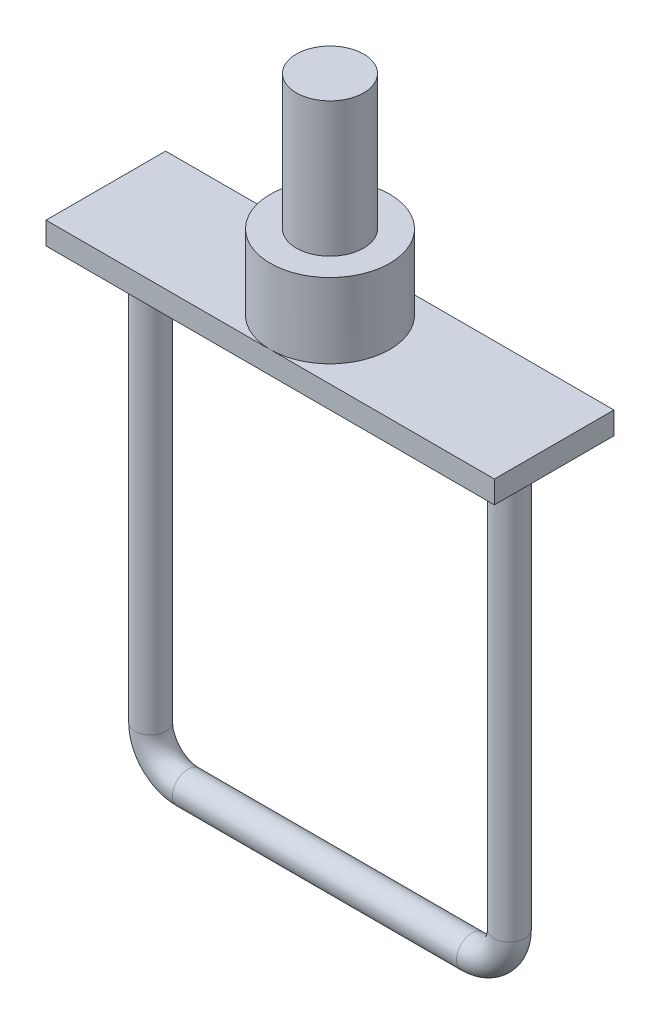
SolidWorks part; units mm, degrees
ref_plane "Front Plane" through (0, 0, 0) normal (0, 0, 1) x (1, 0, 0)
ref_plane "Top Plane" through (0, 0, 0) normal (0, 1, 0) x (1, 0, 0)
ref_plane "Right Plane" through (0, 0, 0) normal (1, 0, 0) x (0, 0, -1)
sketch "Sketch1" plane through (0, 0, 0) normal (0, 1, 0) x (1, 0, 0)
  circle A0 centre (0, 0) radius 2.25
  dimension "D1" = 4.5
extrude "Boss-Extrude1" add sketch "Sketch1" along normal blind 9 contours A0
sketch "Sketch2" plane through (0, 0, 0) normal (0, -1, 0) x (1, 0, 0)
  circle A0 centre (0, 0) radius 4
  dimension "D1" = 8
extrude "Boss-Extrude2" add sketch "Sketch2" along normal blind 5
sketch "Sketch3" plane through (0, 0, 0) normal (0, 0, 1) x (1, 0, 0)
  line L0 (-15, -5) -> (15, -5)
  line L2 (-4, -5) -> (4, -5) construction
  point P3 (0, -5)
  dimension "D1" = 30
extrude "Extrude-Thin1" add sketch "Sketch3" along normal blind 4 thin thin type one direction wall 1.5
ref_plane "Plane1" through (0, 0, 0) normal (0, 0, -1) x (-1, 0, 0)
mirror "Mirror1" about plane through (0, 0, 0) normal (0, 0, -1) of "Extrude-Thin1"
sketch "Sketch4" plane through (0, -5, 0) normal (0, 1, 0) x (1, 0, 0)
  line L0 (55, 0) -> (-55, 0) construction
  line L1 (15, -4) -> (15, 4) construction
  line L2 (-15, -4) -> (-15, 4) construction
  circle A0 centre (12, 0) radius 1.04
  circle A1 centre (-12, 0) radius 1.04
  dimension "D1" = 2.08
  dimension "D2" = 3
  dimension "D3" = 3
extrude "Cut-Extrude1" cut sketch "Sketch4" against normal through all
sketch "Sketch5" plane through (0, 0, 0) normal (0, 0, 1) x (1, 0, 0)
  line L0 (-12, -6.5) -> (-12, -34.6)
  line L1 (-13.04, -6.5) -> (-10.96, -6.5) construction
  line L2 (12, -6.5) -> (12, -34.6)
  line L3 (-9.5, -37.1) -> (9.5, -37.1)
  arc A0 (-12, -34.6) -> (-9.5, -37.1) centre (-9.5, -34.6) ccw
  arc A1 (9.5, -37.1) -> (12, -34.6) centre (9.5, -34.6) ccw
  point P5 (10.96, -6.5)
  point P7 (13.04, -6.5)
  dimension "D5" = 19
  dimension "D6" = 28.1
sketch "Sketch6" plane through (0, -6.5, 0) normal (0, -1, 0) x (1, 0, 0)
  circle A0 centre (-12, 0) radius 1.04
sweep "Sweep1" add profiles "Sketch6" path "Sketch5"
sketch "Sketch7" plane through (0, -6.5, 0) normal (0, 1, 0) x (1, 0, 0)
  circle A0 centre (-12, 0) radius 1.04
  circle A1 centre (12, 0) radius 1.04
extrude "Boss-Extrude3" add sketch "Sketch7" along normal up to surface (1.5 mm away) up to face at (-12, -5, 1.04)
